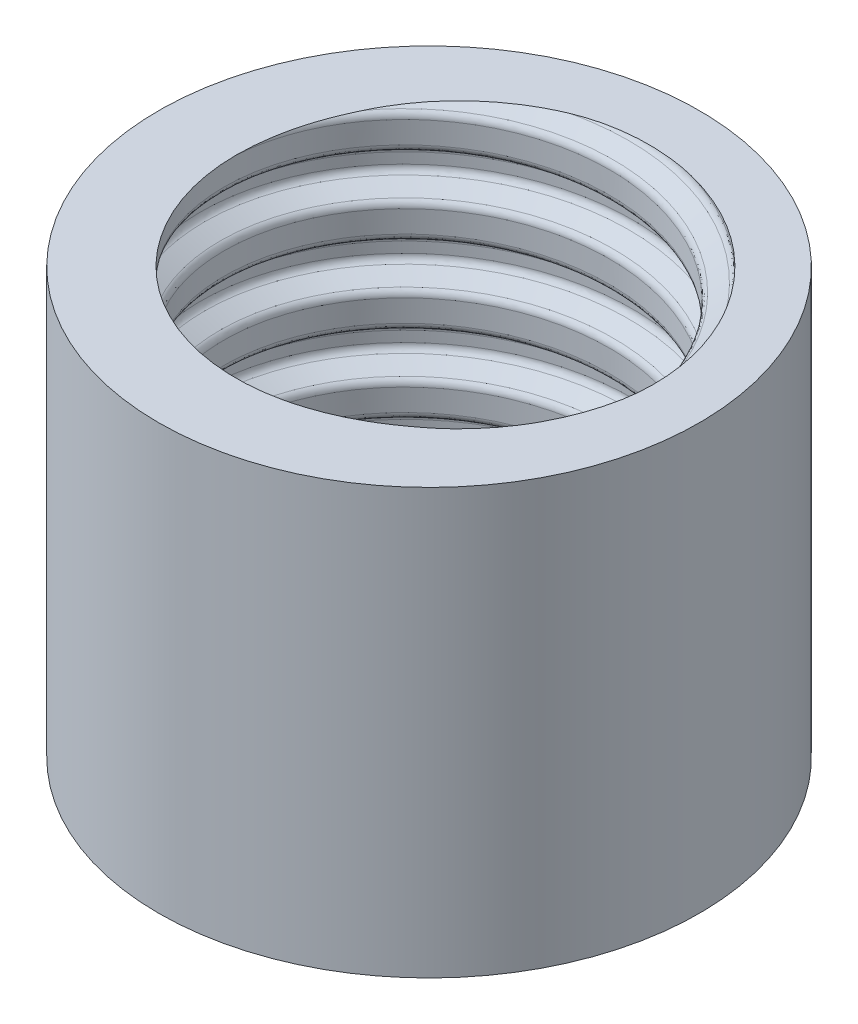
SolidWorks part; units mm, degrees
material "6061-T6 (SS)"
ref_plane "Front Plane" through (0, 0, 0) normal (0, 0, 1) x (1, 0, 0)
ref_plane "Top Plane" through (0, 0, 0) normal (0, 1, 0) x (1, 0, 0)
ref_plane "Right Plane" through (0, 0, 0) normal (1, 0, 0) x (0, 0, -1)
sketch "Sketch1" plane through (0, 0, 0) normal (0, 1, 0) x (1, 0, 0)
  circle A0 centre (0, 0) radius 12.7
  dimension "D1" = 25.4
extrude "Boss-Extrude2" add sketch "Sketch1" along normal blind 22.86 contours A0
shell "Shell3" thickness 5.08 removed face at (0, 22.86, 12.7) outward yes
thread "Thread2" pitch 5.08 method cut profile "Thread Profile2" start angle 0, offset 0, length 22.86, pitch 5.08, diameter 25.4
ref_plane "Plane2" through (12.7, 0, 0) normal (0, 0, 1) x (1, 0, 0)
sketch "Thread Profile2" plane through (12.7, 0, 0) normal (0, 0, 1) x (1, 0, 0)
  line L0 (0, 0) -> (0, 5.08) construction
  line L1 (0, 0) -> (0, 3.6346)
  line L2 (0.508, 3.6346) -> (1.524, 3.6346) construction
  line L3 (1.524, 2.1681) -> (1.524, 1.4665)
  line L4 (1.27, 2.6081) -> (0.254, 3.1946)
  line L5 (1.27, 1.0265) -> (0.254, 0.4399)
  line L6 (0.508, 0) -> (1.524, 0) construction
  arc A0 (0.254, 3.1946) -> (0, 3.6346) centre (0.508, 3.6346) cw
  arc A1 (0.254, 0.4399) -> (0, 0) centre (0.508, 0) ccw
  arc A2 (1.524, 1.4665) -> (1.27, 1.0265) centre (1.016, 1.4665) cw
  arc A3 (1.524, 2.1681) -> (1.27, 2.6081) centre (1.016, 2.1681) ccw
  point P10 (1.524, 2.4614)
  point P17 (1.524, 1.1732)
  point P18 (0, 3.3413)
  point P19 (0, 0.2933)
  point P20 (0, 0)
  dimension "RootFillet1" = 0.508
  dimension "RootFillet2" = 0.508
  dimension "CrestFillet2" = 0.508
  dimension "CrestFillet1" = 0.508
  dimension "Pitch" = 5.08
  dimension "Angle1" = 30
  dimension "Angle2" = 30
  dimension "a" = 3.048
  dimension "b" = 1.524
  dimension "c" = 1.2882
